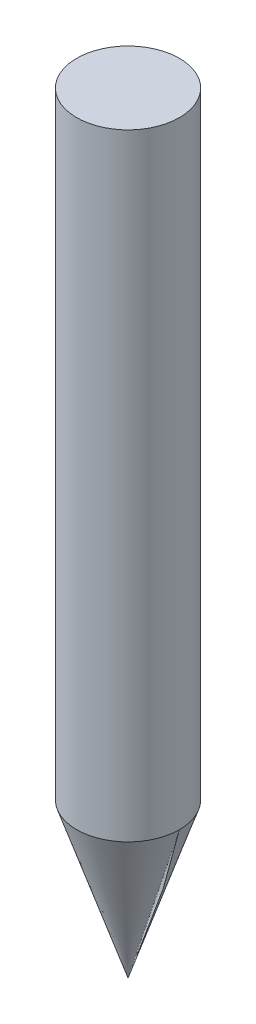
SolidWorks part; units mm, degrees
material "Brass"
ref_plane "Front Plane" through (0, 0, 0) normal (0, 0, 1) x (1, 0, 0)
ref_plane "Top Plane" through (0, 0, 0) normal (0, 1, 0) x (1, 0, 0)
ref_plane "Right Plane" through (0, 0, 0) normal (1, 0, 0) x (0, 0, -1)
sketch "Sketch1" plane through (0, 0, 0) normal (0, 0, 1) x (1, 0, 0)
  line L0 (0, 0) -> (0, 60) construction
  line L1 (0, 0) -> (4, 12)
  line L2 (4, 12) -> (4, 60)
  line L3 (4, 60) -> (0, 60)
  line L4 (0, 60) -> (0, 0)
  dimension "D1" = 4
  dimension "D2" = 12
  dimension "D3" = 48
  dimension "D4" = 4
revolve "Revolve1" add sketch "Sketch1" angle 360 about L0
